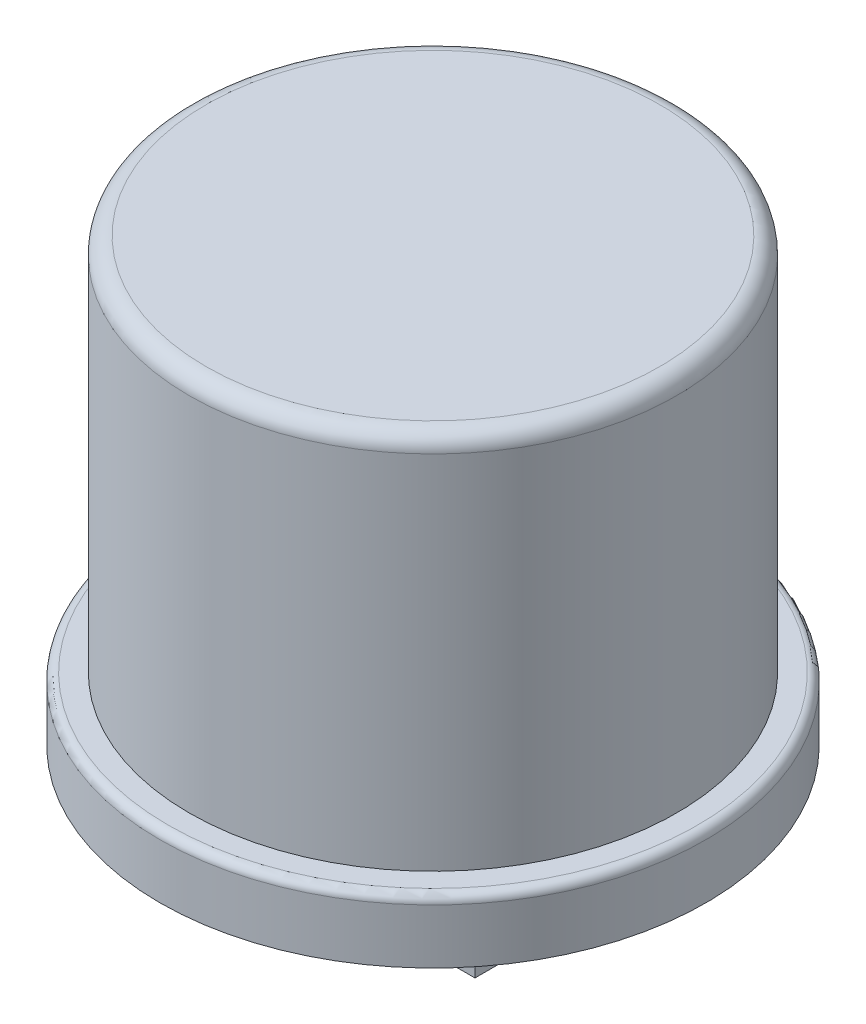
SolidWorks part; units mm, degrees
ref_plane "Front Plane" through (0, 0, 0) normal (0, 0, 1) x (1, 0, 0)
ref_plane "Top Plane" through (0, 0, 0) normal (0, 1, 0) x (1, 0, 0)
ref_plane "Right Plane" through (0, 0, 0) normal (1, 0, 0) x (0, 0, -1)
sketch "Sketch1" plane through (0, 0, 0) normal (0, 1, 0) x (1, 0, 0)
  circle A0 centre (0, 0) radius 6.5
  dimension "D1" = 13
extrude "Boss-Extrude1" add sketch "Sketch1" along normal blind 1.5
sketch "Sketch2" plane through (0, 1.5, 0) normal (0, 1, 0) x (1, 0, 0)
  circle A0 centre (0, 0) radius 5.8
  dimension "D1" = 11.6
extrude "Boss-Extrude2" add sketch "Sketch2" along normal blind 9
fillet "Fillet1" radius 0.4 1 edges at (0, 10.5, 5.8)
sketch "Sketch3" plane through (0, 0, 0) normal (0, -1, 0) x (1, 0, 0)
  circle A0 centre (0, 0) radius 5
  dimension "D1" = 10
extrude "Cut-Extrude1" cut sketch "Sketch3" against normal blind 4.8
sketch "Sketch4" plane through (0, 4.8, 0) normal (0, -1, 0) x (1, 0, 0)
  line L0 (-4.991, 0.3) -> (-2.9, 0.3)
  line L1 (-4.991, -0.3) -> (-2.9, -0.3)
  line L2 (-5, 0) -> (5, 0) construction
  line L3 (-2.9, 0.3) -> (-2.9, -0.3)
  line L4 (0, -0.825) -> (0, 0.825) construction
  line L5 (2.9, 0.3) -> (2.9, -0.3)
  line L6 (4.991, -0.3) -> (2.9, -0.3)
  line L7 (4.991, 0.3) -> (2.9, 0.3)
  line L8 (0, 5) -> (0, -5) construction
  line L9 (-0.3, 4.991) -> (-0.3, 2.7)
  line L10 (0.3, 4.991) -> (0.3, 2.7)
  line L11 (0.3, 2.7) -> (-0.3, 2.7)
  line L12 (0.3, -2.7) -> (-0.3, -2.7)
  line L13 (0.3, -4.991) -> (0.3, -2.7)
  line L14 (-0.3, -4.991) -> (-0.3, -2.7)
  circle A0 centre (0, 0) radius 5 construction
  circle A1 centre (0, 0) radius 5 construction
  arc A2 (-0.3, -4.991) -> (0.3, -4.991) centre (0, 0) ccw
  circle A3 centre (0, 0) radius 5
  arc A4 (-4.991, 0.3) -> (-4.991, -0.3) centre (0, 0) ccw
  arc A5 (4.991, -0.3) -> (4.991, 0.3) centre (0, 0) ccw
  arc A6 (0.3, 4.991) -> (-0.3, 4.991) centre (0, 0) ccw
  point P11 (-2.9, 0)
  point P25 (0, 2.7)
  dimension "D1" = 5.8
  dimension "D2" = 0.6
  dimension "D3" = 5.4
  dimension "D4" = 0
extrude "Boss-Extrude3" add sketch "Sketch4" along normal up to surface (4.8 mm away) up to face at (0, 0, -5)
sketch "Sketch5" plane through (0, 4.8, 0) normal (0, -1, 0) x (1, 0, 0)
  line L0 (-2.9, 0.3) -> (-2.9, -0.3) construction
  line L1 (-1, 2.7) -> (1, 2.7)
  line L2 (-1, 2.7) -> (-1, 1.9)
  line L3 (-1, 1.9) -> (1, 1.9)
  line L4 (1, 2.7) -> (1, 1.9)
  line L5 (-2.9, 1.9) -> (-1.9, 1.9)
  line L6 (-2.9, 1.9) -> (-2.9, -1.9)
  line L7 (-2.9, -1.9) -> (-1.9, -1.9)
  line L8 (-1.9, 1.9) -> (-1.9, -1.9)
  line L9 (0.3, 2.7) -> (-0.3, 2.7) construction
  line L10 (0, -0.825) -> (0, 0.825) construction
  line L11 (1.9, 1.9) -> (1.9, -1.9)
  line L12 (2.9, -1.9) -> (1.9, -1.9)
  line L13 (2.9, 1.9) -> (2.9, -1.9)
  line L14 (2.9, 1.9) -> (1.9, 1.9)
  line L15 (0.825, 0) -> (-0.825, 0) construction
  line L16 (1, -2.7) -> (1, -1.9)
  line L17 (-1, -1.9) -> (1, -1.9)
  line L18 (-1, -2.7) -> (-1, -1.9)
  line L19 (-1, -2.7) -> (1, -2.7)
  point P4 (0, 2.7)
  point P10 (-1.9, 0)
  dimension "D1" = 3.8
  dimension "D2" = 2
  dimension "D3" = 1
extrude "Boss-Extrude4" add sketch "Sketch5" along normal blind 7.2
sketch "Sketch6" plane through (0, 0, 1.9) normal (0, 0, 1) x (1, 0, 0)
  line L0 (-1.9, -1.4) -> (-1.6, -1.7)
  line L1 (-1.9, -2.4) -> (-1.9, 4.8) construction
  line L2 (-1.6, -1.7) -> (-2.4, -2.4)
  line L3 (-1.9, -2.4) -> (-2.9, -2.4) construction
  line L4 (-2.9, -2.4) -> (-2.9, 4.8) construction
  line L5 (-1.9, -1.4) -> (-1.9, -2.4)
  line L6 (-1.9, -2.4) -> (-2.4, -2.4)
  line L7 (0, -0.825) -> (0, 0.825) construction
  line L8 (1.9, -2.4) -> (2.4, -2.4)
  line L9 (1.9, -1.4) -> (1.9, -2.4)
  line L10 (1.6, -1.7) -> (2.4, -2.4)
  line L11 (1.9, -1.4) -> (1.6, -1.7)
  line M2 (1.9, 4.8) -> (1.9, -2.4)
  line M3 (1.9, -2.4) -> (2.9, -2.4)
  dimension "D1" = 1.3
  dimension "D2" = 1
  dimension "D3" = 0.7
extrude "Cut-Extrude2" cut sketch "Sketch6" against normal up to next contours L6 L5 L2 | L10 L9 M3 region at (-2.0667, -2.2542, 1.9) region at (2.0667, -2.2542, 1.9)
extrude "Boss-Extrude5" add sketch "Sketch6<3>" against normal up to surface (3.8 mm away) contours L0 L5 L2 | L11 L10 M2 region at (-1.8, -1.6875, 1.9) region at (1.8, -1.6875, 1.9) up to face at (2.4, 0.5675, -1.9)
sketch "Sketch6<3>" plane through (0, 0, 1.9) normal (0, 0, 1) x (1, 0, 0) same geometry as "Sketch6"
fillet "Fillet2" radius 0.1 2 edges at (1.6, -1.7, 0) (-1.6, -1.7, 0)
fillet "Fillet3" radius 0.2 1 edges at (0, 1.5, 6.5)
